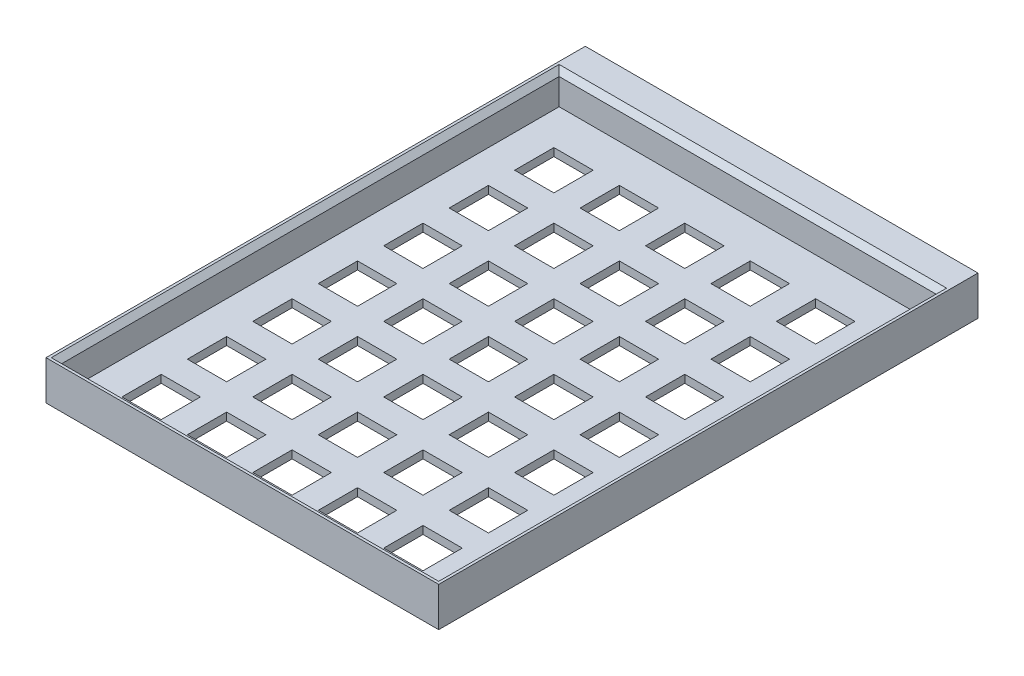
SolidWorks part; units mm, degrees
ref_plane "Front Plane" through (0, 0, 0) normal (0, 0, 1) x (1, 0, 0)
ref_plane "Top Plane" through (0, 0, 0) normal (0, 1, 0) x (1, 0, 0)
ref_plane "Right Plane" through (0, 0, 0) normal (1, 0, 0) x (0, 0, -1)
sketch "Sketch1" plane through (0, 0, 0) normal (0, 0, 1) x (1, 0, 0)
  line L0 (75, 15) -> (75, 0)
  line L1 (0, 0) -> (150, 0)
  line L2 (0, 0) -> (0, 15)
  line L3 (0, 15) -> (150, 15)
  line L4 (150, 0) -> (150, 15)
  line L6 (100, 11.5) -> (50, 11.5)
  line L7 (100, 11.5) -> (100, 3.5)
  line L8 (100, 3.5) -> (50, 3.5)
  line L9 (50, 11.5) -> (50, 3.5)
  line L10 (100, 11.5) -> (50, 3.5) construction
  line L11 (100, 3.5) -> (50, 11.5) construction
  point P7 (75, 7.5)
  dimension "D1" = 150
  dimension "D2" = 15
  dimension "D3" = 50
  dimension "8" = 8
extrude "Boss-Extrude1" add sketch "Sketch1" along normal blind 206 contours L2 L3 L4 L1
sketch "Sketch2" plane through (0, 15, 0) normal (0, 1, 0) x (1, 0, 0)
  line L0 (71, -115.9315) -> (71, -193)
  line L1 (0, -206) -> (150, -206) construction
  line L2 (0, -206) -> (0, 0) construction
  line L4 (147, -13) -> (3, -13)
  line L5 (147, -13) -> (147, -203)
  line L6 (147, -203) -> (3, -203)
  line L7 (3, -13) -> (3, -203)
  line L8 (71, -23) -> (18.0919, -23)
  line L9 (13, -104.2395) -> (13, -176.1278)
  line L12 (134.4631, -23) -> (81, -23)
  line L13 (18.0919, -23) -> (71, -96)
  line L14 (81, -96) -> (134.4631, -23)
  line L15 (137, -104.2395) -> (137, -175.3972)
  line L18 (13, -23.8722) -> (13, -94.2395)
  line L19 (13, -23.8722) -> (64, -94.2395)
  line L20 (13, -176.1278) -> (67.1015, -104.2395)
  line L21 (137, -175.3972) -> (86.5704, -104.2395)
  line L22 (137, -24.6028) -> (86, -94.2395)
  line L23 (137, -24.6028) -> (137, -94.2395)
  line L24 (81, -109.9315) -> (137, -193)
  line L25 (13, -193) -> (71, -115.9315)
  line L26 (137, -193) -> (13, -193)
  line L32 (13, -104.2395) -> (67.1015, -104.2395)
  line L34 (137, -94.2395) -> (86, -94.2395)
  line L35 (71, -23) -> (71, -96)
  line L36 (71, -193) -> (81, -193)
  line L37 (81, -193) -> (81, -109.9315)
  line L40 (64, -94.2395) -> (13, -94.2395)
  line L41 (86.5704, -104.2395) -> (137, -104.2395)
  line L42 (81, -96) -> (81, -23)
  point P6 (75, -100)
  point P14 (75, -13)
  point P24 (12, -100)
  point P34 (75, -13)
  point P37 (12, -100)
  dimension "D1" = 144
  dimension "D2" = 190
  dimension "D3" = 10
  dimension "D4" = 10
  dimension "D5" = 10
  dimension "D6" = 3
  dimension "D7" = 10
  dimension "D8" = 3
  dimension "D9" = 10
  dimension "D10" = 10
  dimension "D11" = 10
  dimension "D12" = 10
  dimension "D13" = 10
  dimension "D14" = 73
  dimension "D15" = 73
  dimension "D16" = 180
  dimension "D17" = 180
  dimension "D18" = 180
  dimension "D19" = 51
  dimension "D20" = 51
extrude "Cut-Extrude1" cut sketch "Sketch2" against normal blind 12 contours L4 L7 L6 L5
extrude "Cut-Extrude3" cut sketch "Sketch1<3>" along normal blind 6 contours L6 L9 L8 L7
sketch "Sketch1<3>" plane through (0, 0, 0) normal (0, 0, 1) x (1, 0, 0) same geometry as "Sketch1"
sketch "Sketch3" plane through (0, 3.5, 0) normal (0, 1, 0) x (1, 0, 0)
  line L0 (75, 0) -> (75, -8)
  line L1 (0, 0) -> (150, 0) construction
  line L2 (100, 0) -> (50, 0) construction
  line L3 (90, -2) -> (60, -2)
  line L4 (90, -2) -> (90, -6)
  line L5 (90, -6) -> (60, -6)
  line L6 (60, -2) -> (60, -6)
  line L7 (90, -2) -> (60, -6) construction
  line L8 (90, -6) -> (60, -2) construction
  point P4 (75, -4)
  dimension "D1" = 2
  dimension "D2" = 30
  dimension "D3" = 4
extrude "Cut-Extrude4" cut sketch "Sketch3" against normal blind 2 contours L6 L5 L4 L3
chamfer "Chamfer1" distance 6 angle 30 1 edges at (75, 11.5, 6) first distance on face at (75, 11.5, 3)
chamfer "Chamfer2" distance 2 angle 45 4 edges at (75, 15, 203) (3, 15, 108) (75, 15, 13) (147, 15, 108)
sketch "Sketch4" plane through (0, 3, 0) normal (0, 1, 0) x (1, 0, 0)
  line L0 (3, -13) -> (3, -203) construction
  line L1 (15.5, -27.5) -> (30.5, -27.5)
  line L2 (15.5, -27.5) -> (15.5, -42.5)
  line L3 (15.5, -42.5) -> (30.5, -42.5)
  line L4 (30.5, -27.5) -> (30.5, -42.5)
  line L5 (147, -13) -> (3, -13) construction
  line L6 (40.5, -27.5) -> (55.5, -27.5)
  line L7 (40.5, -27.5) -> (40.5, -42.5)
  line L8 (40.5, -42.5) -> (55.5, -42.5)
  line L9 (55.5, -27.5) -> (55.5, -42.5)
  line L10 (65.5, -27.5) -> (80.5, -27.5)
  line L11 (65.5, -27.5) -> (65.5, -42.5)
  line L12 (65.5, -42.5) -> (80.5, -42.5)
  line L13 (80.5, -27.5) -> (80.5, -42.5)
  line L14 (90.5, -27.5) -> (105.5, -27.5)
  line L15 (90.5, -27.5) -> (90.5, -42.5)
  line L16 (90.5, -42.5) -> (105.5, -42.5)
  line L17 (105.5, -27.5) -> (105.5, -42.5)
  line L18 (115.5, -27.5) -> (130.5, -27.5)
  line L19 (115.5, -27.5) -> (115.5, -42.5)
  line L20 (115.5, -42.5) -> (130.5, -42.5)
  line L21 (130.5, -27.5) -> (130.5, -42.5)
  line L22 (40.5, -52.5) -> (55.5, -52.5)
  line L23 (40.5, -52.5) -> (40.5, -67.5)
  line L24 (40.5, -67.5) -> (55.5, -67.5)
  line L25 (55.5, -52.5) -> (55.5, -67.5)
  line L26 (65.5, -52.5) -> (80.5, -52.5)
  line L27 (65.5, -52.5) -> (65.5, -67.5)
  line L28 (65.5, -67.5) -> (80.5, -67.5)
  line L29 (80.5, -52.5) -> (80.5, -67.5)
  line L30 (90.5, -52.5) -> (105.5, -52.5)
  line L31 (90.5, -52.5) -> (90.5, -67.5)
  line L32 (90.5, -67.5) -> (105.5, -67.5)
  line L33 (105.5, -52.5) -> (105.5, -67.5)
  line L34 (115.5, -52.5) -> (130.5, -52.5)
  line L35 (115.5, -52.5) -> (115.5, -67.5)
  line L36 (115.5, -67.5) -> (130.5, -67.5)
  line L37 (130.5, -52.5) -> (130.5, -67.5)
  line L38 (40.5, -77.5) -> (55.5, -77.5)
  line L39 (40.5, -77.5) -> (40.5, -92.5)
  line L40 (40.5, -92.5) -> (55.5, -92.5)
  line L41 (55.5, -77.5) -> (55.5, -92.5)
  line L42 (65.5, -77.5) -> (80.5, -77.5)
  line L43 (65.5, -77.5) -> (65.5, -92.5)
  line L44 (65.5, -92.5) -> (80.5, -92.5)
  line L45 (80.5, -77.5) -> (80.5, -92.5)
  line L46 (90.5, -77.5) -> (105.5, -77.5)
  line L47 (90.5, -77.5) -> (90.5, -92.5)
  line L48 (90.5, -92.5) -> (105.5, -92.5)
  line L49 (105.5, -77.5) -> (105.5, -92.5)
  line L50 (115.5, -77.5) -> (130.5, -77.5)
  line L51 (115.5, -77.5) -> (115.5, -92.5)
  line L52 (115.5, -92.5) -> (130.5, -92.5)
  line L53 (130.5, -77.5) -> (130.5, -92.5)
  line L54 (40.5, -102.5) -> (55.5, -102.5)
  line L55 (40.5, -102.5) -> (40.5, -117.5)
  line L56 (40.5, -117.5) -> (55.5, -117.5)
  line L57 (55.5, -102.5) -> (55.5, -117.5)
  line L58 (65.5, -102.5) -> (80.5, -102.5)
  line L59 (65.5, -102.5) -> (65.5, -117.5)
  line L60 (65.5, -117.5) -> (80.5, -117.5)
  line L61 (80.5, -102.5) -> (80.5, -117.5)
  line L62 (90.5, -102.5) -> (105.5, -102.5)
  line L63 (90.5, -102.5) -> (90.5, -117.5)
  line L64 (90.5, -117.5) -> (105.5, -117.5)
  line L65 (105.5, -102.5) -> (105.5, -117.5)
  line L66 (115.5, -102.5) -> (130.5, -102.5)
  line L67 (115.5, -102.5) -> (115.5, -117.5)
  line L68 (115.5, -117.5) -> (130.5, -117.5)
  line L69 (130.5, -102.5) -> (130.5, -117.5)
  line L70 (40.5, -127.5) -> (55.5, -127.5)
  line L71 (40.5, -127.5) -> (40.5, -142.5)
  line L72 (40.5, -142.5) -> (55.5, -142.5)
  line L73 (55.5, -127.5) -> (55.5, -142.5)
  line L74 (65.5, -127.5) -> (80.5, -127.5)
  line L75 (65.5, -127.5) -> (65.5, -142.5)
  line L76 (65.5, -142.5) -> (80.5, -142.5)
  line L77 (80.5, -127.5) -> (80.5, -142.5)
  line L78 (90.5, -127.5) -> (105.5, -127.5)
  line L79 (90.5, -127.5) -> (90.5, -142.5)
  line L80 (90.5, -142.5) -> (105.5, -142.5)
  line L81 (105.5, -127.5) -> (105.5, -142.5)
  line L82 (115.5, -127.5) -> (130.5, -127.5)
  line L83 (115.5, -127.5) -> (115.5, -142.5)
  line L84 (115.5, -142.5) -> (130.5, -142.5)
  line L85 (130.5, -127.5) -> (130.5, -142.5)
  line L86 (40.5, -152.5) -> (55.5, -152.5)
  line L87 (40.5, -152.5) -> (40.5, -167.5)
  line L88 (40.5, -167.5) -> (55.5, -167.5)
  line L89 (55.5, -152.5) -> (55.5, -167.5)
  line L90 (65.5, -152.5) -> (80.5, -152.5)
  line L91 (65.5, -152.5) -> (65.5, -167.5)
  line L92 (65.5, -167.5) -> (80.5, -167.5)
  line L93 (80.5, -152.5) -> (80.5, -167.5)
  line L94 (90.5, -152.5) -> (105.5, -152.5)
  line L95 (90.5, -152.5) -> (90.5, -167.5)
  line L96 (90.5, -167.5) -> (105.5, -167.5)
  line L97 (105.5, -152.5) -> (105.5, -167.5)
  line L98 (115.5, -152.5) -> (130.5, -152.5)
  line L99 (115.5, -152.5) -> (115.5, -167.5)
  line L100 (115.5, -167.5) -> (130.5, -167.5)
  line L101 (130.5, -152.5) -> (130.5, -167.5)
  line L102 (40.5, -177.5) -> (55.5, -177.5)
  line L103 (40.5, -177.5) -> (40.5, -192.5)
  line L104 (40.5, -192.5) -> (55.5, -192.5)
  line L105 (55.5, -177.5) -> (55.5, -192.5)
  line L106 (65.5, -177.5) -> (80.5, -177.5)
  line L107 (65.5, -177.5) -> (65.5, -192.5)
  line L108 (65.5, -192.5) -> (80.5, -192.5)
  line L109 (80.5, -177.5) -> (80.5, -192.5)
  line L110 (90.5, -177.5) -> (105.5, -177.5)
  line L111 (90.5, -177.5) -> (90.5, -192.5)
  line L112 (90.5, -192.5) -> (105.5, -192.5)
  line L113 (105.5, -177.5) -> (105.5, -192.5)
  line L114 (115.5, -177.5) -> (130.5, -177.5)
  line L115 (115.5, -177.5) -> (115.5, -192.5)
  line L116 (115.5, -192.5) -> (130.5, -192.5)
  line L117 (130.5, -177.5) -> (130.5, -192.5)
  line L118 (15.5, -52.5) -> (30.5, -52.5)
  line L119 (15.5, -52.5) -> (15.5, -67.5)
  line L120 (15.5, -67.5) -> (30.5, -67.5)
  line L121 (30.5, -52.5) -> (30.5, -67.5)
  line L122 (15.5, -77.5) -> (30.5, -77.5)
  line L123 (15.5, -77.5) -> (15.5, -92.5)
  line L124 (15.5, -92.5) -> (30.5, -92.5)
  line L125 (30.5, -77.5) -> (30.5, -92.5)
  line L126 (15.5, -102.5) -> (30.5, -102.5)
  line L127 (15.5, -102.5) -> (15.5, -117.5)
  line L128 (15.5, -117.5) -> (30.5, -117.5)
  line L129 (30.5, -102.5) -> (30.5, -117.5)
  line L130 (15.5, -127.5) -> (30.5, -127.5)
  line L131 (15.5, -127.5) -> (15.5, -142.5)
  line L132 (15.5, -142.5) -> (30.5, -142.5)
  line L133 (30.5, -127.5) -> (30.5, -142.5)
  line L134 (15.5, -152.5) -> (30.5, -152.5)
  line L135 (15.5, -152.5) -> (15.5, -167.5)
  line L136 (15.5, -167.5) -> (30.5, -167.5)
  line L137 (30.5, -152.5) -> (30.5, -167.5)
  line L138 (15.5, -177.5) -> (30.5, -177.5)
  line L139 (15.5, -177.5) -> (15.5, -192.5)
  line L140 (15.5, -192.5) -> (30.5, -192.5)
  line L141 (30.5, -177.5) -> (30.5, -192.5)
  dimension "D1" = 15
  dimension "D2" = 12.5
  dimension "D3" = 14.5
  dimension "D4" = 7
extrude "Cut-Extrude5" cut sketch "Sketch4" against normal blind 4
